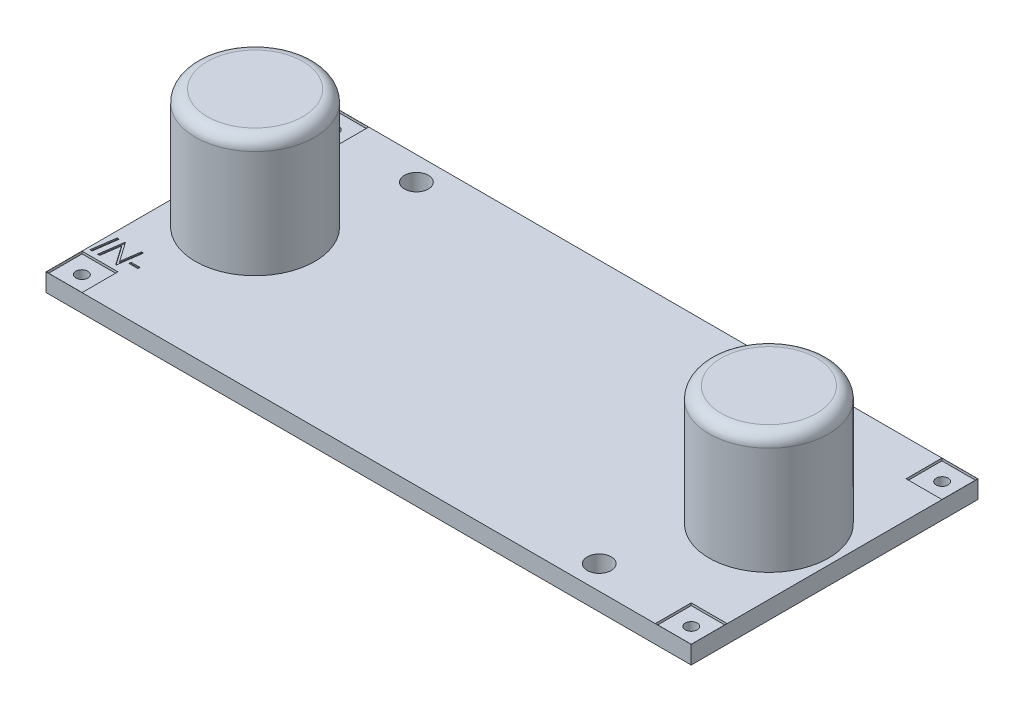
SolidWorks part; units mm, degrees
ref_plane "Front Plane" through (0, 0, 0) normal (0, 0, 1) x (1, 0, 0)
ref_plane "Top Plane" through (0, 0, 0) normal (0, 1, 0) x (1, 0, 0)
ref_plane "Right Plane" through (0, 0, 0) normal (1, 0, 0) x (0, 0, -1)
sketch "Sketch1" plane through (0, 0, 0) normal (0, 1, 0) x (1, 0, 0)
  line L1 (0, 0) -> (54, 0)
  line L2 (0, 0) -> (0, -24)
  line L3 (0, -24) -> (54, -24)
  line L4 (54, 0) -> (54, -24)
  dimension "D1" = 54
  dimension "D2" = 24
extrude "Boss-Extrude1" add sketch "Sketch1" along normal blind 1.5
sketch "Sketch2" plane through (0, 1.5, 0) normal (0, 1, 0) x (1, 0, 0)
  line L0 (0, 0) -> (0, -24) construction
  line L1 (54, 0) -> (0, 0) construction
  line L2 (54, -24) -> (54, 0) construction
  line L3 (0, -24) -> (54, -24) construction
  circle A0 centre (9, -2) radius 1
  circle A1 centre (44.3, -22) radius 1
  dimension "D1" = 2
  dimension "D4" = 2
  dimension "D5" = 9.7
  dimension "D6" = 2
  dimension "D2" = 9
  dimension "D3" = 2
extrude "Cut-Extrude1" cut sketch "Sketch2" against normal up to next
sketch "Sketch4" plane through (0, 1.5, 0) normal (0, 1, 0) x (1, 0, 0)
  line L0 (54, 0) -> (0, 0) construction
  line L1 (0.01, -0.01) -> (3.01, -0.01)
  line L2 (0.01, -0.01) -> (0.01, -3.01)
  line L3 (0.01, -3.01) -> (3.01, -3.01)
  line L4 (3.01, -0.01) -> (3.01, -3.01)
  line L5 (0, 0) -> (0, -24) construction
  line L6 (27, 0) -> (27, -24) construction
  line L7 (0, -24) -> (54, -24) construction
  line L8 (0, -12) -> (54, -12) construction
  line L9 (54, -24) -> (54, 0) construction
  line L10 (53.99, -0.01) -> (53.99, -3.01)
  line L11 (53.99, -0.01) -> (50.99, -0.01)
  line L12 (53.99, -3.01) -> (50.99, -3.01)
  line L13 (50.99, -0.01) -> (50.99, -3.01)
  line L14 (0.01, -23.99) -> (0.01, -20.99)
  line L15 (0.01, -23.99) -> (3.01, -23.99)
  line L16 (3.01, -23.99) -> (3.01, -20.99)
  line L17 (0.01, -20.99) -> (3.01, -20.99)
  line L18 (53.99, -23.99) -> (50.99, -23.99)
  line L19 (53.99, -23.99) -> (53.99, -20.99)
  line L20 (50.99, -23.99) -> (50.99, -20.99)
  line L21 (53.99, -20.99) -> (50.99, -20.99)
  dimension "D1" = 3
  dimension "D2" = 3
  dimension "D3" = 0.01
  dimension "D4" = 0.01
extrude "Cut-Extrude2" cut sketch "Sketch4" against normal blind 0.2
sketch "Sketch5" plane through (0, 0, 0) normal (0, -1, 0) x (1, 0, 0)
  line L0 (54, 0) -> (0, 0) construction
  line L1 (54, 24) -> (54, 0) construction
  line L2 (27, 0) -> (27, 24) construction
  line L3 (0, 24) -> (54, 24) construction
  line L4 (0, 12) -> (54, 12) construction
  line L5 (0, 0) -> (0, 24) construction
  circle A0 centre (52.5, 1.5) radius 0.5
  circle A1 centre (52.5, 22.5) radius 0.5
  circle A2 centre (1.5, 1.5) radius 0.5
  circle A3 centre (1.5, 22.5) radius 0.5
  dimension "D1" = 1
  dimension "D2" = 1.5
  dimension "D3" = 1.5
extrude "Cut-Extrude3" cut sketch "Sketch5" against normal up to next
sketch "Sketch8" plane through (0, 1.5, 0) normal (0, 1, 0) x (1, 0, 0)
  text T0 "<i>IN+</i>" font "Century Gothic" height 2
extrude "Cut-Extrude4" cut sketch "Sketch8" against normal blind 0.1
sketch "Sketch9" plane through (0, 1.5, 0) normal (0, 1, 0) x (1, 0, 0)
  text T0 "<i>IN-</i>" font "Century Gothic" height 2
extrude "Cut-Extrude5" cut sketch "Sketch9" against normal blind 0.1
sketch "Sketch10" plane through (0, 1.5, 0) normal (0, 1, 0) x (1, 0, 0)
  line L0 (0, 0) -> (0, -24) construction
  line L1 (54, 0) -> (0, 0) construction
  line L2 (27, 0) -> (27, -24) construction
  line L3 (0, -24) -> (54, -24) construction
  circle A0 centre (5.5, -12) radius 5
  circle A1 centre (48.5, -12) radius 5
  dimension "D1" = 10
  dimension "D2" = 5.5
  dimension "D3" = 12
extrude "Boss-Extrude2" add sketch "Sketch10" along normal blind 10
fillet "Fillet1" radius 1 2 edges at (5.5, 11.5, 17) (48.5, 11.5, 7)
